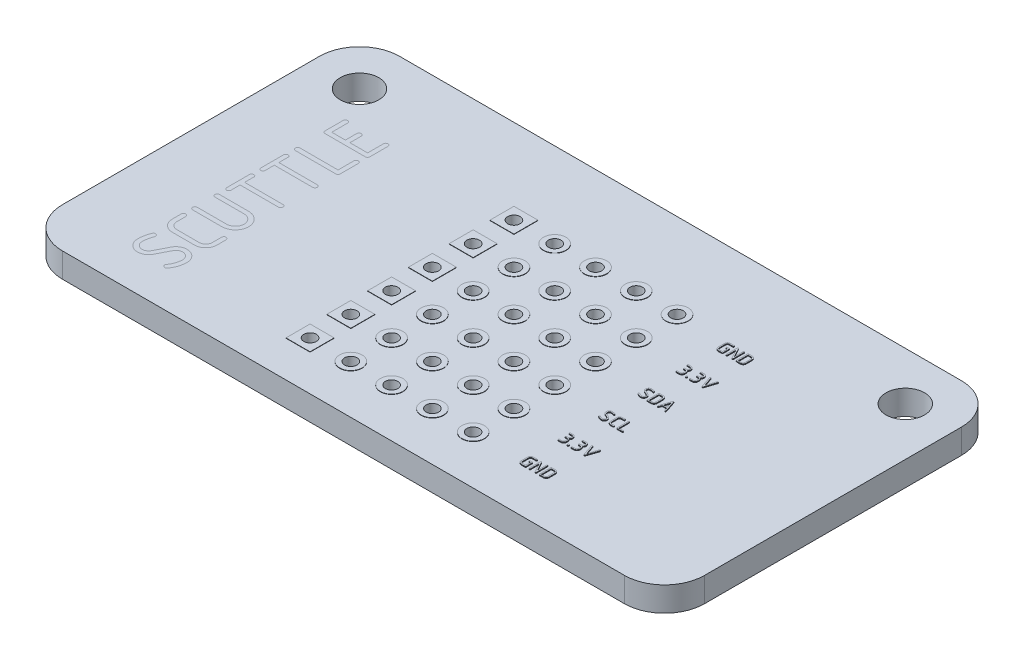
SolidWorks part; units mm, degrees
ref_plane "Front Plane" through (0, 0, 0) normal (0, 0, 1) x (1, 0, 0)
ref_plane "Top Plane" through (0, 0, 0) normal (0, 1, 0) x (1, 0, 0)
ref_plane "Right Plane" through (0, 0, 0) normal (1, 0, 0) x (0, 0, -1)
sketch "Sketch1" plane through (0, 0, 0) normal (0, 1, 0) x (1, 0, 0)
  line L1 (-20, -10.5) -> (20, -10.5)
  line L2 (-20, -10.5) -> (-20, 10.5)
  line L3 (-20, 10.5) -> (20, 10.5)
  line L4 (20, -10.5) -> (20, 10.5)
  line L5 (-20, -10.5) -> (20, 10.5) construction
  line L6 (-20, 10.5) -> (20, -10.5) construction
  point P0 (0, 0)
  dimension "D1" = 21
  dimension "D2" = 40
extrude "boss main" add sketch "Sketch1" along normal blind 1.53
fillet "fillet corners" radius 2.5 4 edges at (-20, 0.765, 10.5) (-20, 0.765, -10.5) (20, 0.765, -10.5) (20, 0.765, 10.5)
sketch "Sketch2" plane through (0, 1.53, 0) normal (0, 1, 0) x (1, 0, 0)
  line L0 (-17, 7.5) -> (17, 7.5) construction
  line L1 (17.5, 10.5) -> (-17.5, 10.5) construction
  circle A0 centre (-17, 7.5) radius 1.2
  circle A1 centre (17, 7.5) radius 1.2
  point P2 (0, 7.5)
  dimension "D3" = 2.4
  dimension "D1" = 34
  dimension "D2" = 3
extrude "cut mounting holes" cut sketch "Sketch2" against normal through all
sketch "Sketch3" plane through (0, 1.53, 0) normal (0, 1, 0) x (1, 0, 0)
  line L0 (-5.08, 5.2) -> (5.08, 5.2) construction
  line L1 (0, 0) -> (0, 5.2) construction
  line L2 (17.5, 10.5) -> (-17.5, 10.5) construction
  circle A0 centre (-5.08, 5.2) radius 0.4
  circle A1 centre (-2.54, 5.2) radius 0.4
  circle A2 centre (0, 5.2) radius 0.4
  circle A3 centre (2.54, 5.2) radius 0.4
  circle A4 centre (5.08, 5.2) radius 0.4
  dimension "D1" = 0.8
  dimension "D2" = 2.54
  dimension "D3" = 2.54
  dimension "D4" = 2.54
  dimension "D5" = 2.54
  dimension "D6" = 5.3
extrude "via top row" cut sketch "Sketch3" against normal through all
pattern_linear "via pattern" count 6 spacing 2.54 along (0, 0, 1) of "via top row"
sketch "Sketch4" plane through (0, 1.53, 0) normal (0, 1, 0) x (1, 0, 0)
  line L0 (-13, -8.5) -> (-13, 6.2303) construction
  line L1 (-17.5, -10.5) -> (17.5, -10.5) construction
  line L2 (-20, 8) -> (-20, -8) construction
  text T0 "SCUTTLE" font "DS ISO 1" height 2.8
  dimension "D1" = 2
  dimension "D2" = 7
split line "Split Line1"
sketch "Sketch5" plane through (0, 1.53, 0) normal (0, 1, 0) x (1, 0, 0)
  line L0 (8.08, 4.5) -> (16.0156, 4.5) construction
  circle A0 centre (5.08, 5.2) radius 0.4 construction
  text T0 "GND\r\n3.3V\r\nSDA\r\nSCL\r\n3.3V\r\nGND" font "DS ISO 1" height 0.76
  dimension "D2" = 0.7
  dimension "D1" = 3
extrude "Boss-Extrude2" add sketch "Sketch5" along normal blind 0.05
sketch "Sketch7" plane through (0, 1.53, 0) normal (0, 1, 0) x (1, 0, 0)
  circle A14 centre (-2.54, 5.2) radius 0.39
  circle A15 centre (-2.54, 5.2) radius 0.7
  circle A16 centre (-2.54, 5.2) radius 0.7
  circle A17 centre (-2.54, 5.2) radius 0.4 construction
  dimension "D3" = 0.01
  dimension "D2" = 0.3
extrude "boss via plating" add sketch "Sketch7" against normal offset from surface (1.57 mm away) 0.02 from offset 0.02 up to face at (-2.54, 0, -2.26) offset beyond the face yes
pattern_linear "boss via plating pattern" count 4 spacing 2.54 along (1, 0, 0) count 6 spacing 2.54 along (0, 0, 1) of "boss via plating"
sketch "Sketch8" plane through (0, 1.53, 0) normal (0, 1, 0) x (1, 0, 0)
  line L1 (-5.83, 4.45) -> (-4.33, 4.45)
  line L2 (-5.83, 4.45) -> (-5.83, 5.95)
  line L3 (-5.83, 5.95) -> (-4.33, 5.95)
  line L4 (-4.33, 4.45) -> (-4.33, 5.95)
  line L5 (-5.83, 4.45) -> (-4.33, 5.95) construction
  line L6 (-5.83, 5.95) -> (-4.33, 4.45) construction
  circle A0 centre (-5.08, 5.2) radius 0.39
  circle A1 centre (-5.08, 5.2) radius 0.4 construction
  point P0 (-5.08, 5.2)
  dimension "D1" = 0.01
  dimension "D2" = 1.5
extrude "Boss-Extrude4" add sketch "Sketch8" against normal offset from surface (1.57 mm away) 0.02 from offset 0.02 up to face at (5.08, 0, 6.8) offset beyond the face yes
pattern_linear "LPattern3" count 6 spacing 2.54 along (0, 0, 1) of "Boss-Extrude4"
equation "\"2.510.00mm\"=10"
equation "\"holeSpace\"=2.54"
equation "\"D2@Sketch3\"=\"holeSpace\""
equation "\"D4@Sketch3\"=\"holeSpace\""
equation "\"D5@Sketch3\"=\"holeSpace\""
